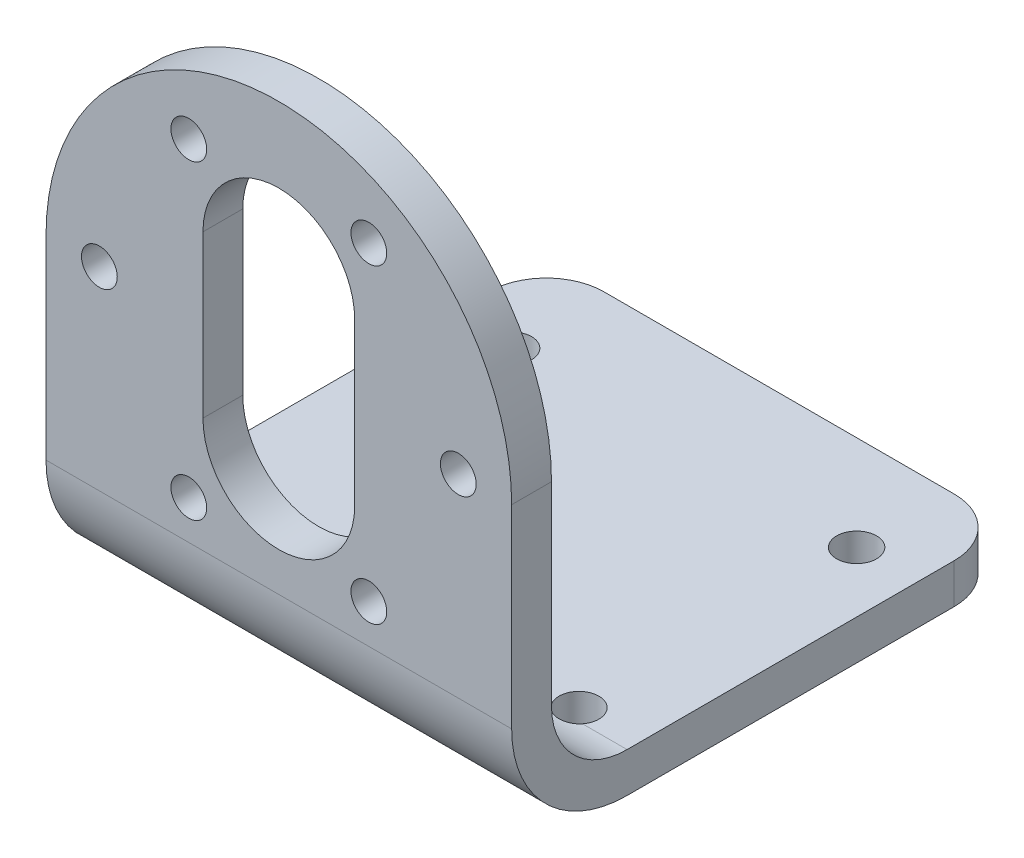
SolidWorks part; units mm, degrees
ref_plane "Front Plane" through (0, 0, 0) normal (0, 0, 1) x (1, 0, 0)
ref_plane "Top Plane" through (0, 0, 0) normal (0, 1, 0) x (1, 0, 0)
ref_plane "Right Plane" through (0, 0, 0) normal (1, 0, 0) x (0, 0, -1)
sketch "Sketch1" plane through (0, 0, 0) normal (0, 1, 0) x (1, 0, 0)
  line L1 (-47.1412, -7.433) -> (-6.7912, -7.433)
  line L2 (-47.1412, -7.433) -> (-47.1412, -50.783)
  line L3 (-47.1412, -50.783) -> (-6.7912, -50.783)
  line L4 (-6.7912, -7.433) -> (-6.7912, -50.783)
extrude "Boss-Extrude1" add sketch "Sketch1" along normal blind 47
sketch "Sketch3" plane through (0, 0, 50.783) normal (0, 0, 1) x (1, 0, 0)
  line L6 (-47.1412, 26.825) -> (-47.1412, 47)
  line L7 (-47.1412, 47) -> (-6.7912, 47)
  line L8 (-6.7912, 26.825) -> (-6.7912, 47)
  arc A1 (-6.7912, 26.825) -> (-47.1412, 26.825) centre (-26.9662, 26.825) ccw
  line M2 (-6.7912, 0) -> (-6.7912, 47)
  line M3 (-6.7912, 47) -> (-47.1412, 47)
  line M4 (-47.1412, 47) -> (-47.1412, 0)
extrude "Cut-Extrude2" cut sketch "Sketch3" against normal blind 102 contours A1 L7 M4 | A1 M2 M3 region at (-11.2977, 42.4936, 50.783) region at (-42.6348, 42.4936, 50.783)
fillet "Fillet1" radius 10 1 edges at (-26.9662, 0, 50.783)
sketch "Sketch5" plane through (-47.1412, 0, 0) normal (-1, 0, 0) x (0, 0, 1)
  line L0 (7.433, 0) -> (-6.6658, 0)
  line L1 (-6.6658, 0) -> (-6.6658, 3.45)
  line L2 (50.783, 47) -> (50.783, 59.7784)
  line L3 (50.783, 59.7784) -> (47.333, 59.7784)
  line L5 (-6.6658, 3.45) -> (36.5956, 3.45)
  line L6 (-6.6658, 3.45) -> (-6.6658, 59.7784)
  line L7 (-6.6658, 59.7784) -> (47.333, 59.7784)
  line L8 (47.333, 17.5785) -> (47.333, 59.7784)
  line L9 (36.5956, 3.45) -> (40.783, 3.45)
  line L12 (47.333, 10) -> (47.333, 17.5785)
  arc A1 (40.783, 3.45) -> (47.333, 10) centre (40.783, 10) ccw
  line M2 (50.783, 26.825) -> (7.433, 26.825)
  line M3 (7.433, 26.825) -> (7.433, 0)
extrude "Cut-Extrude3" cut sketch "Sketch5" against normal blind 102 contours L8 L7 L6 L5 M2 M3 | L5 L8 M2 M3 region at (-47.1412, 15.2394, 27.1987) region at (-47.1412, 38.9007, 17.2162)
fillet "Fillet2" radius 5 2 edges at (-6.7912, 1.725, 7.433) (-47.1412, 1.725, 7.433)
sketch "Sketch6" plane through (0, 3.45, 0) normal (0, 1, 0) x (1, 0, 0)
  line L0 (-27.9141, -7.433) -> (-27.9141, -13.933)
  line L1 (-42.1412, -7.433) -> (-11.7912, -7.433) construction
  line L2 (-47.1412, -24.2783) -> (-43.6412, -24.2783)
  line L3 (-47.1412, -12.433) -> (-47.1412, -40.783) construction
  line L4 (-6.7912, -25.5422) -> (-10.2912, -25.5422)
  line L5 (-6.7912, -12.433) -> (-6.7912, -40.783) construction
  line L6 (-43.6412, -24.2783) -> (-43.6412, -13.933)
  line L7 (-43.6412, -13.933) -> (-10.2912, -13.933)
  line L8 (-10.2912, -13.933) -> (-10.2912, -45.493)
  line L9 (-10.2912, -45.493) -> (-43.6412, -45.493)
  line L10 (-43.6412, -45.493) -> (-43.6412, -24.2783)
  line L11 (-41.9112, -17.393) -> (-41.9112, -37.993)
  line L12 (-12.0212, -17.393) -> (-12.0212, -37.993)
  circle A0 centre (-41.9112, -15.663) radius 1.73
  circle A1 centre (-12.0212, -15.663) radius 1.73
  circle A2 centre (-41.9112, -39.723) radius 1.73
  circle A3 centre (-12.0212, -39.723) radius 1.73
  line M12 (-47.1412, -40.783) -> (-6.7912, -40.783)
extrude "Cut-Extrude4" cut sketch "Sketch6" against normal blind 102 and the other way blind 102 contours A3 M12 | A3 M12 | A2 M12 | A2 M12 | A1 | A0 region at (-41.9112, 3.45, 15.663) region at (-41.9112, 3.45, 39.5133) region at (-41.9112, 3.45, 41.056) region at (-12.0212, 3.45, 15.663) region at (-12.0212, 3.45, 41.056) region at (-12.0212, 3.45, 39.5133)
sketch "Sketch7" plane through (0, 0, 50.783) normal (0, 0, 1) x (1, 0, 0)
  line L0 (-47.1412, 21.9829) -> (-33.5412, 21.9829)
  line L2 (-33.5412, 33.925) -> (-33.5412, 19.945)
  line L4 (-20.3912, 33.925) -> (-20.3912, 19.945)
  line L5 (-47.1412, 26.825) -> (-47.1412, 10) construction
  line L6 (-20.3912, 20.4169) -> (-6.7912, 20.4169)
  line L7 (-6.7912, 26.825) -> (-6.7912, 10) construction
  line L8 (-26.9662, 47) -> (-26.9662, 40.5)
  arc A0 (-6.7912, 26.825) -> (-47.1412, 26.825) centre (-26.9662, 26.825) ccw construction
  arc A1 (-20.3912, 33.925) -> (-33.5412, 33.925) centre (-26.9662, 33.925) ccw
  arc A2 (-33.5412, 19.945) -> (-20.3912, 19.945) centre (-26.9662, 19.945) ccw
extrude "Cut-Extrude5" cut sketch "Sketch7" against normal blind 102 contours L2 A2 L4 A1 region at (-26.9662, 26.935, 50.783)
sketch "Sketch8" plane through (0, 0, 50.783) normal (0, 0, 1) x (1, 0, 0)
  line L4 (-40.9662, 26.825) -> (-44.0662, 26.825)
  line L5 (-12.9662, 26.825) -> (-9.8662, 26.825)
  arc A0 (-33.8891, 38.9936) -> (-20.0433, 38.9936) centre (-26.9662, 26.825) ccw
  arc A1 (-35.5437, 41.6181) -> (-18.3887, 41.6181) centre (-26.9662, 26.825) ccw
  arc A2 (-20.0433, 14.6564) -> (-20.0519, 14.6448) centre (-26.9662, 19.725) cw
  arc A3 (-33.8806, 39.0052) -> (-33.8891, 38.9936) centre (-26.9662, 33.925) ccw
  circle A4 centre (-34.7662, 40.2772) radius 1.55
  circle A5 centre (-19.1662, 40.2772) radius 1.55
  circle A6 centre (-19.1662, 13.3728) radius 1.55
  arc A7 (-20.0433, 38.9936) -> (-20.0519, 39.0052) centre (-26.9662, 33.925) ccw
  circle A8 centre (-34.7662, 13.3728) radius 1.55
  arc A9 (-33.8806, 14.6448) -> (-33.8891, 14.6564) centre (-26.9662, 19.725) cw
  circle A10 centre (-42.5162, 26.825) radius 1.55
  circle A11 centre (-11.4162, 26.825) radius 1.55
extrude "Cut-Extrude6" cut sketch "Sketch8" against normal blind 102 contours A8 | A6 | L5 A11 | L5 A11 | L4 A10 | L4 A10 | A4 | A5 A4 region at (-42.5162, 26.1672, 50.783) region at (-42.5162, 27.4828, 50.783) region at (-34.7662, 40.2772, 50.783) region at (-34.7662, 13.3728, 50.783) region at (-19.1662, 13.3728, 50.783) region at (-11.4162, 26.1672, 50.783) region at (-11.4162, 27.4828, 50.783) region at (-19.1662, 40.2772, 50.783)
